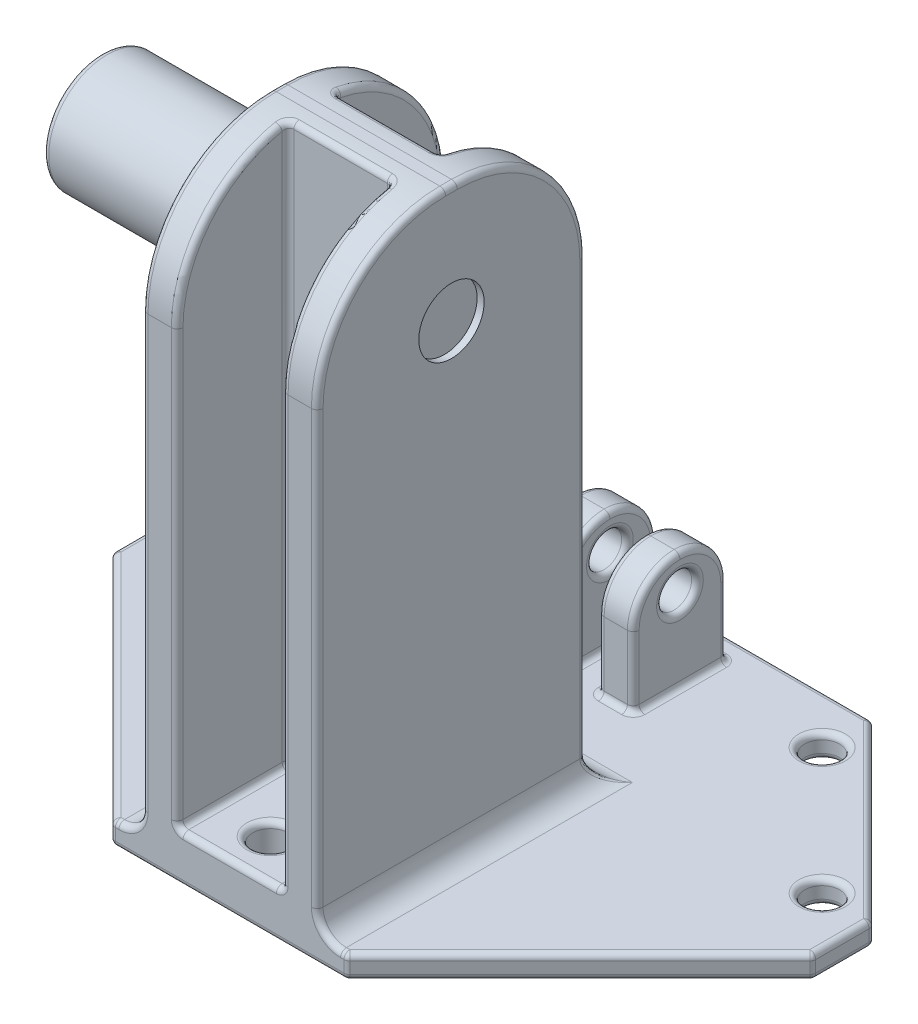
SolidWorks part; units mm, degrees
ref_plane "Front Plane" through (0, 0, 0) normal (0, 0, 1) x (1, 0, 0)
ref_plane "Top Plane" through (0, 0, 0) normal (0, 1, 0) x (1, 0, 0)
ref_plane "Right Plane" through (0, 0, 0) normal (1, 0, 0) x (0, 0, -1)
sketch "Sketch1" plane through (0, 0, 0) normal (0, 1, 0) x (1, 0, 0)
  line L0 (-30, -12.5) -> (-30, 12.5)
  line L1 (-30, 12.5) -> (-15, 27.5)
  line L2 (-15, 27.5) -> (15, 27.5)
  line L3 (15, 27.5) -> (30, 12.5)
  line L4 (30, 12.5) -> (30, -12.5)
  line L5 (30, -12.5) -> (-30, -12.5)
  point P3 (0, -12.5)
  point P8 (0, 27.5)
  point P10 (30, 0)
  dimension "D1" = 45
  dimension "D2" = 60
  dimension "D3" = 25
  dimension "D4" = 15
extrude "Boss-Extrude1" add sketch "Sketch1" along normal blind 2
sketch "Sketch2" plane through (0, 2, 0) normal (0, 1, 0) x (1, 0, 0)
  line L0 (0, 0) -> (0, 27.5) construction
  line L1 (15, 27.5) -> (-15, 27.5) construction
  line L2 (0, 38.2574) -> (-41.2957, -3.0384) construction
  line L3 (0, 38.2574) -> (44.8535, -6.5961) construction
  line L4 (-15, 27.5) -> (-30, 12.5) construction
  line L5 (30, 12.5) -> (15, 27.5) construction
  circle A0 centre (-15.0301, 23.2273) radius 1.5
  circle A1 centre (-25.8488, 12.4086) radius 1.5
  circle A2 centre (15.0301, 23.2273) radius 1.5
  circle A3 centre (25.8488, 12.4086) radius 1.5
  dimension "D2" = 3
  dimension "D3" = 21.2557
  dimension "D1" = 3
  dimension "D4" = 15.3
extrude "Cut-Extrude1" cut sketch "Sketch2" against normal through all
sketch "Sketch3" plane through (0, 2, 0) normal (0, 1, 0) x (1, 0, 0)
  line L0 (0, 0) -> (0, 27.5) construction
  line L1 (15, 27.5) -> (-15, 27.5) construction
  line L3 (-4.5, 17.5764) -> (-1.5, 17.5764)
  line L4 (-4.5, 17.5764) -> (-4.5, 25.5764)
  line L5 (-4.5, 25.5764) -> (-1.5, 25.5764)
  line L6 (-1.5, 17.5764) -> (-1.5, 25.5764)
  line L7 (-4.5, 17.5764) -> (-1.5, 25.5764) construction
  line L8 (-4.5, 25.5764) -> (-1.5, 17.5764) construction
  point P5 (-3, 21.5764)
  dimension "D1" = 3
  dimension "D2" = 8
  dimension "D3" = 1.5
extrude "Boss-Extrude2" add sketch "Sketch3" along normal blind 10
sketch "Sketch4" plane through (-4.5, 0, 0) normal (-1, 0, 0) x (0, 0, 1)
  line L0 (-25.5764, 12) -> (-17.5764, 12) construction
  circle A0 centre (-21.5764, 9) radius 1.5
  point P5 (-21.5764, 12)
  dimension "D2" = 3
  dimension "D1" = 3
extrude "Cut-Extrude2" cut sketch "Sketch4" against normal through all
fillet "Fillet1" radius 4 2 edges at (-3, 12, -17.5764) (-3, 12, -25.5764)
mirror "Mirror2" about plane through (0, 0, 0) normal (1, 0, 0) of "Cut-Extrude2", "Fillet1", "Boss-Extrude2"
sketch "Sketch6" plane through (0, 2, 0) normal (0, 1, 0) x (1, 0, 0)
  line L0 (-30, -12.5) -> (30, -12.5) construction
  line L1 (7.5, 10.5) -> (-7.5, 10.5)
  line L2 (7.5, 10.5) -> (7.5, -12.5)
  line L3 (7.5, -12.5) -> (-7.5, -12.5)
  line L4 (-7.5, 10.5) -> (-7.5, -12.5)
  line L5 (7.5, 10.5) -> (-7.5, -12.5) construction
  line L6 (7.5, -12.5) -> (-7.5, 10.5) construction
  point P0 (0, -1)
  point P8 (0, -12.5)
  dimension "D1" = 23
  dimension "D2" = 15
extrude "Boss-Extrude4" add sketch "Sketch6" along normal blind 50
ref_plane "Plane1" through (0, 0, 1) normal (0, 0, 1) x (1, 0, 0)
sketch "Sketch7" plane through (-7.5, 0, 0) normal (-1, 0, 0) x (0, 0, 1)
  circle A0 centre (1, 42) radius 5
  dimension "D1" = 10
extrude "Boss-Extrude5" add sketch "Sketch7" along normal blind 15
fillet "Fillet2" radius 11 2 edges at (0, 52, -10.5) (0, 52, 12.5)
sketch "Sketch9" plane through (7.5, 0, 0) normal (1, 0, 0) x (0, 0, -1)
  circle A0 centre (-1, 42) radius 2.8
  dimension "D1" = 5.6
extrude "Cut-Extrude4" cut sketch "Sketch9" against normal blind 0.6
chamfer "Chamfer1" distance 20 angle 45 2 edges at (30, 1, 12.5) (-30, 1, 12.5)
ref_plane "Plane2" through (0, 4, 0) normal (0, 1, 0) x (1, 0, 0)
sketch "Sketch8" plane through (0, 4, 0) normal (0, 1, 0) x (1, 0, 0)
  line L0 (7.5, 10.5) -> (-7.5, 10.5) construction
  line L1 (4.5, 10.5) -> (-4.5, 10.5)
  line L2 (4.5, 10.5) -> (4.5, 1)
  line L3 (4.5, 1) -> (-4.5, 1)
  line L4 (-4.5, 10.5) -> (-4.5, 1)
  line L6 (-7.5, 10.5) -> (-7.5, -12.5) construction
  line L7 (7.5, -0.5) -> (7.5, 10.5) construction
  line L8 (-28.6, -1) -> (28.6, -1) construction
  line L9 (7.5, -12.5) -> (-7.5, -12.5) construction
  line L10 (-4.5, -12.5) -> (4.5, -12.5)
  line L11 (-4.5, -12.5) -> (-4.5, -3)
  line L12 (-4.5, -3) -> (4.5, -3)
  line L13 (4.5, -12.5) -> (4.5, -3)
  dimension "D1" = 2
  dimension "D2" = 3
  dimension "D3" = 3
  dimension "D4" = 2
extrude "Cut-Extrude3" cut sketch "Sketch8" along normal through all
sketch "Sketch11" plane through (0, 0, 0) normal (0, -1, 0) x (1, 0, 0)
  circle A0 centre (0, 9.0041) radius 1.52
extrude "Cut-Extrude5" cut sketch "Sketch11" against normal through all contours A0
fillet "Fillet4" radius 2 3 edges at (-7.5, 2, 1) (0, 2, -10.5) (7.5, 2, 1)
fillet "Fillet3" radius 0.5 100 edges at (4.5, 22.5, -10.5) (-4.5, 22.5, -10.5) (-4.5, 22.5, 12.5) (4.5, 22.5, 12.5) (4.5, 48.2284, -7.7916) (-4.5, 48.2284, -7.7916) (-4.5, 48.2284, 9.7916) (4.5, 48.2284, 9.7916) (1.5, 5, -25.5764) (1.5, 10.8284, -24.4049) (1.5, 10.8284, -18.748) (1.5, 5, -17.5764) (1.5, 9, -20.0764) (-1.5, 5, -25.5764) (-1.5, 5, -17.5764) (-1.5, 10.8284, -18.748) (-1.5, 10.8284, -24.4049) (-1.5, 9, -20.0764) (4.5, 5, -25.5764) (4.5, 5, -17.5764) (4.5, 10.8284, -18.748) (4.5, 10.8284, -24.4049) (4.5, 9, -20.0764) (-4.5, 5, -25.5764) (-4.5, 10.8284, -24.4049) (-4.5, 10.8284, -18.748) (-4.5, 5, -17.5764) (-4.5, 9, -20.0764) (0, 51.8972, -1) (-4.5, 27.9486, -1) (0, 4, -1) (4.5, 27.9486, -1) (0, 51.8972, 3) (4.5, 27.9486, 3) (0, 4, 3) (-4.5, 27.9486, 3) (-22.5, 42, 6) (-7.5, 22.5, 12.5) (-7.5, 22.5, -10.5) (-7.5, 48.7782, -7.2782) (-7.5, 48.7782, 9.2782) (7.5, 22.5, 12.5) (7.5, 48.7782, 9.2782) (7.5, 48.7782, -7.2782) (7.5, 22.5, -10.5) (15, 1, -27.5) (-15, 1, -27.5) (30, 1, -12.5) (30, 1, -7.5) (22.5, 0, -20) (0, 0, -27.5) (-22.5, 0, -20) (-30, 0, -10) (-20, 0, 2.5) (0, 0, 12.5) (20, 0, 2.5) (30, 0, -10) (-15.0301, 0, -21.7273) (-25.8488, 0, -10.9086) (15.0301, 0, -21.7273) (25.8488, 0, -10.9086) (-9.75, 2, 12.5) (-20, 2, 2.5) (-30, 2, -10) (-22.5, 2, -20) (0, 2, -27.5) (22.5, 2, -20) (30, 2, -10) (20, 2, 2.5) (9.75, 2, 12.5) (4.5, 2, -21.5764) (3, 2, -25.5764) (1.5, 2, -21.5764) (3, 2, -17.5764) (-15.0301, 2, -21.7273) (-25.8488, 2, -10.9086) (15.0301, 2, -21.7273) (25.8488, 2, -10.9086) (-3, 2, -25.5764) (-4.5, 2, -21.5764) (-3, 2, -17.5764) (-1.5, 2, -21.5764) (10, 1, 12.5) (-10, 1, 12.5) (-30, 1, -7.5) (-30, 1, -12.5) (-7.5, 52, 1) (7.5, 52, 1) (0, 0, 7.4841) (0, 4, 7.4841) (8.0858, 2.5858, -11.0858) (8.0858, 2.5858, 12.5) (-8.0858, 2.5858, -11.0858) (-8.0858, 2.5858, 12.5) (-4.5, 4, 7.75) (4.5, 4, 7.75) (0, 4, 12.5) (-4.5, 4, -5.75) (4.5, 4, -5.75) (0, 4, -10.5)
